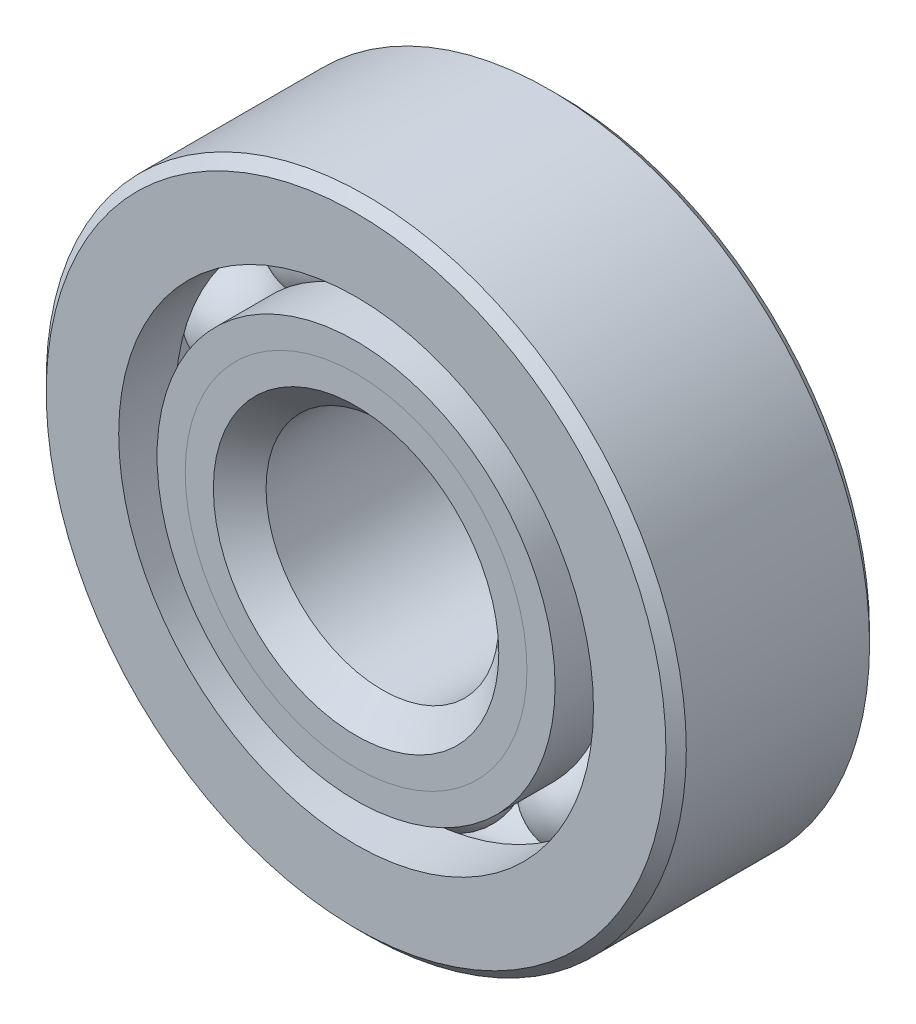
SolidWorks part; units mm, degrees
ref_plane "Front Plane" through (0, 0, 0) normal (0, 0, 1) x (1, 0, 0)
ref_plane "Top Plane" through (0, 0, 0) normal (0, 1, 0) x (1, 0, 0)
ref_plane "Right Plane" through (0, 0, 0) normal (1, 0, 0) x (0, 0, -1)
sketch "Sketch1" plane through (0, 0, 0) normal (1, 0, 0) x (0, 0, -1)
  line L0 (-3.5, 0) -> (3.5, 0) construction
  line L1 (0, 11) -> (0, -11) construction
  line L2 (3.15, 11) -> (-3.15, 11)
  line L3 (-3.15, 11) -> (-3.5, 10.65)
  line L4 (-3.5, 10.65) -> (-3.5, 8.1593)
  line L5 (-3.5, 8.1593) -> (-1.5556, 8.1593)
  line L6 (3.5, 8.1593) -> (1.5556, 8.1593)
  line L7 (3.5, 10.65) -> (3.5, 8.1593)
  line L8 (3.15, 11) -> (3.5, 10.65)
  line L9 (0, 11) -> (0, 7.5) construction
  line L10 (0, 7.5) -> (0, 4) construction
  arc A0 (-1.5556, 8.1593) -> (1.5556, 8.1593) centre (0, 7.5) cw
  point P14 (0, 4)
  dimension "Width" = 7
  dimension "OD" = 22
  dimension "D1" = 45
  dimension "D2" = 0.35
  dimension "D3" = 3.1111
  dimension "D4" = 0.6593
revolve "Revolve1" add sketch "Sketch1" angle 360 about L0
sketch "Sketch2" plane through (0, 0, 0) normal (1, 0, 0) x (0, 0, -1)
  line L0 (-3.5, 6.8407) -> (-1.5556, 6.8407)
  line L1 (-3.5, 10.65) -> (-3.5, -10.65) construction
  line L2 (-3.5, 6.8407) -> (-3.5, 5.8729)
  line L3 (-3.5, 5.8729) -> (-2.5323, 4.9052)
  line L4 (-2.5323, 4.9052) -> (0, 4.9052)
  line L5 (0, 11) -> (0, -11) construction
  line L6 (0, 4.9052) -> (0, 5.8105)
  line L7 (0, 5.8105) -> (0, 4) construction
  line L8 (-3.5, 6.8407) -> (-3.5, 4.9052) construction
  line L9 (-3.5, 4.9052) -> (-2.5323, 4.9052) construction
  arc A0 (-1.5556, 6.8407) -> (0, 5.8105) centre (0, 7.5) ccw
  arc A1 (1.5556, 8.1593) -> (-1.5556, 8.1593) centre (0, 7.5) ccw construction
  circle A2 centre (0, 7.5) radius 1.6895 construction
  dimension "D1" = 45
revolve "Revolve2" add sketch "Sketch2" angle 360 about L0
sketch "Sketch3" plane through (0, 0, 0) normal (1, 0, 0) x (0, 0, -1)
  line L0 (-3.5, 5.8729) -> (-2.5323, 4.9052)
  line L1 (-2.5323, 4.9052) -> (0, 4.9052)
  line L2 (0, 4.9052) -> (0, 5.8105)
  line L3 (-3.5, 5.8729) -> (-3.5, 4.9052)
  line L4 (-3.5, 6.8407) -> (-3.5, 4.9052) construction
  line L5 (-3.5, 4.9052) -> (-2.5948, 4)
  line L6 (-2.5948, 4) -> (3.15, 4)
  line L7 (3.15, 11) -> (3.15, -11) construction
  line L8 (3.15, 4) -> (3.5, 4.35)
  line L9 (3.5, -10.65) -> (3.5, 10.65) construction
  line L10 (3.5, 4.35) -> (3.5, 6.8407)
  line L11 (3.5, 6.8407) -> (1.5556, 6.8407)
  line L13 (3.15, 11) -> (3.5, 10.65) construction
  circle A0 centre (0, 7.5) radius 1.6895 construction
  arc A1 (1.5556, 6.8407) -> (0, 5.8105) centre (0, 7.5) cw
revolve "Revolve3" add sketch "Sketch3" angle 360 about L0
sketch "Sketch4" plane through (0, 0, 0) normal (1, 0, 0) x (0, 0, -1)
  line L0 (-1.6895, 7.5) -> (1.6895, 7.5)
  circle A1 centre (0, 7.5) radius 1.6895 construction
  arc A2 (-1.6895, 7.5) -> (1.6895, 7.5) centre (0, 7.5) cw
  arc A3 (1.5556, 8.1593) -> (-1.5556, 8.1593) centre (0, 7.5) ccw construction
revolve "Revolve4" add sketch "Sketch4" angle 360 about L0
ref_axis "Axis1" through (0, 0, -3.5) along (0, 0, 1)
pattern_circular "CirPattern1" count 10 every 36 about axis through (0, 0, -3.5) along (0, 0, 1) of bodies 104
equation "\"D2@Sketch1\" = \"Width@Sketch1\"*.05"
equation "\"D3@Sketch1\" = \"Width@Sketch1\"/2.25"
equation "\"D4@Sketch1\" = (((\"OD@Sketch1\"-\"Width@Sketch1\")/2)/3.25)/3.5"
equation "\"D2@CirPattern1\" = 360/\"Balls@CirPattern1\""
